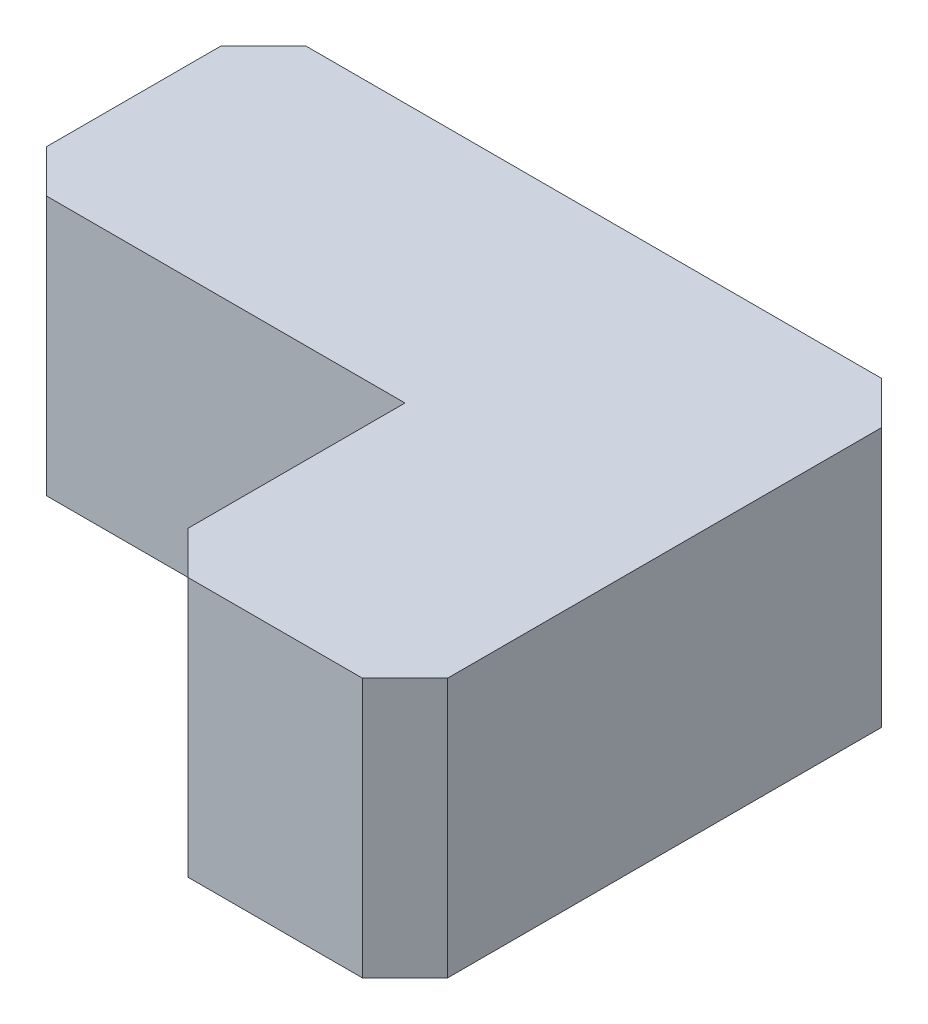
SolidWorks part; units mm, degrees
ref_plane "Front Plane" through (0, 0, 0) normal (0, 0, 1) x (1, 0, 0)
ref_plane "Top Plane" through (0, 0, 0) normal (0, 1, 0) x (1, 0, 0)
ref_plane "Right Plane" through (0, 0, 0) normal (1, 0, 0) x (0, 0, -1)
sketch "Sketch2" plane through (0, 0, 0) normal (0, 1, 0) x (1, 0, 0)
  line L0 (0, 46) -> (9, 55)
  line L1 (9, 0) -> (140, 0)
  line L2 (0, 9) -> (0, 46)
  line L3 (9, 55) -> (131, 55)
  line L4 (140, 0) -> (140, 46)
  line L5 (140, 0) -> (85, 0)
  line L6 (140, 0) -> (140, -46)
  line L7 (131, -55) -> (94, -55)
  line L8 (85, 0) -> (85, -46)
  line L9 (0, 9) -> (9, 0)
  line L10 (94, -55) -> (85, -46)
  line L11 (140, -46) -> (131, -55)
  line L12 (131, 55) -> (140, 46)
  point P0 (0, 0)
  point P1 (140, 55)
  point P2 (0, 55)
  point P5 (85, -55)
  point P6 (140, -55)
  dimension "D1" = 55
  dimension "D2" = 140
  dimension "D3" = 55
  dimension "D4" = 55
extrude "Boss-Extrude1" add sketch "Sketch2" along normal blind 55 contours L12 L3 L0 L2 L9 L1 L4 | L6 L11 L7 L10 L8 L5
shell "Shell1" thickness 3
ref_plane "Plane1" through (0, 41.5, 0) normal (0, 1, 0) x (1, 0, 0)
sketch "Sketch4" plane through (0, 0, 0) normal (0, 0, 1) x (1, 0, 0)
  line L0 (60.5, 41.5) -> (-60.5, 41.5) construction
  line L1 (-7.3258, 41.5) -> (147.3258, 41.5)
  line L2 (-7.3258, 41.5) -> (-7.3258, 64.0976)
  line L3 (-7.3258, 64.0976) -> (147.3258, 64.0976)
  line L4 (147.3258, 41.5) -> (147.3258, 64.0976)
  line L6 (-7.3258, 41.5) -> (147.3258, 41.5)
  line L7 (-7.3258, 41.5) -> (-7.3258, -2.7209)
  line L8 (-7.3258, -2.7209) -> (147.3258, -2.7209)
  line L9 (147.3258, 41.5) -> (147.3258, -2.7209)
equation "\"width of arm\"=55"
equation "\"D1@Sketch2\"=\"width of arm\""
equation "\"height of arm\"= 140"
equation "\"D2@Sketch2\"=\"height of arm\""
equation "\"width connection rotatation\"=55"
equation "\"D3@Sketch2\"=\"width connection rotatation\""
equation "\"length connection rotator\"=55"
equation "\"D4@Sketch2\"=\"length connection rotator\""
